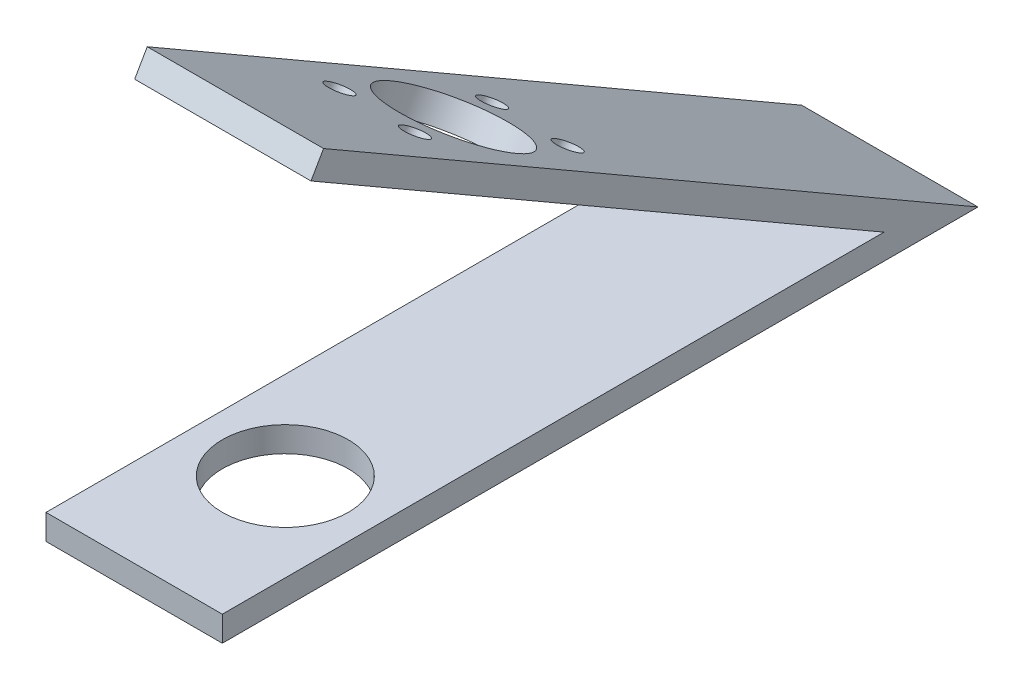
SolidWorks part; units mm, degrees
ref_plane "Front Plane" through (0, 0, 0) normal (0, 0, 1) x (1, 0, 0)
ref_plane "Top Plane" through (0, 0, 0) normal (0, 1, 0) x (1, 0, 0)
ref_plane "Right Plane" through (0, 0, 0) normal (1, 0, 0) x (0, 0, -1)
sketch "Sketch1" plane through (0, 0, 0) normal (1, 0, 0) x (0, 0, -1)
  line L0 (-227.4871, 131.3397) -> (0, 0)
  line L1 (0, 0) -> (-262.6795, 0)
  line L2 (-262.6795, 0) -> (-262.6795, -10)
  line L3 (-262.6795, -10) -> (37.3205, -10)
  line L4 (37.3205, -10) -> (-222.4871, 140)
  line L5 (-222.4871, 140) -> (-227.4871, 131.3397)
  dimension "D1" = 10
  dimension "D2" = 10
  dimension "D3" = 300
  dimension "D4" = 300
  dimension "D5" = 30
extrude "Boss-Extrude1" add sketch "Sketch1" along normal blind 70
sketch "Sketch2" plane through (0, 8.6603, -5) normal (0, 0.866, -0.5) x (1, 0, 0)
  line L0 (0, 37.3205) -> (0, -262.6795) construction
  line L4 (70, -262.6795) -> (0, -262.6795) construction
  circle A0 centre (35, -162.6795) radius 25
  dimension "D1" = 50
  dimension "D2" = 35
  dimension "D3" = 100
extrude "Cut-Extrude1" cut sketch "Sketch2" against normal blind 10
sketch "Sketch5" plane through (0, 0, 0) normal (0, 1, 0) x (1, 0, 0)
  line L0 (70, -262.6795) -> (0, -262.6795) construction
  line L1 (70, 37.3205) -> (70, -222.4871) construction
  circle A0 centre (35, -202.6795) radius 25
  dimension "D1" = 50
  dimension "D2" = 60
  dimension "D3" = 35
extrude "Cut-Extrude3" cut sketch "Sketch5" against normal blind 300
sketch "Sketch6" plane through (0, 8.6603, -5) normal (0, 0.866, -0.5) x (1, 0, 0)
  line L5 (70, 37.3205) -> (70, -262.6795) construction
  line L6 (0, 37.3205) -> (0, -262.6795) construction
  circle A0 centre (50, -197.6795) radius 5
  circle A1 centre (20, -197.6795) radius 5
  circle A2 centre (20, -127.6795) radius 5
  circle A3 centre (50, -127.6795) radius 5
  point P0 (35, -162.6795)
  dimension "D2" = 10
  dimension "D3" = 10
  dimension "D4" = 10
  dimension "D5" = 10
  dimension "D1" = 20
  dimension "D6" = 20
  dimension "D7" = 20
  dimension "D8" = 20
extrude "Cut-Extrude5" cut sketch "Sketch6" against normal blind 10
equation "\"mountAngle\" = 30deg"
equation "\"D5@Sketch1\"=\"mountAngle\""
equation "\"ThrusterDim\"= 140mm"
equation "\"hatchHoleDiameter\"= 600mm"
equation "\"hullThickness\"= 120mm"
equation "\"gasketHullInterconnectWidth\"= 100mm"
equation "\"collarThickness\"= 15"
equation "\"hatchTunnelLength\"=200"
equation "\"oRingDiameter\"=2"
equation "\"boltPatternRadiusInterconnect\"=500"
equation "\"interconnectBoltDiameter\"=30"
equation "\"hatchShaftDiameter\"=20"
equation "\"hatchMinima\"=50"
equation "\"hullDiameter\"=2000"
equation "\"hatchMaxima\"=180"
equation "\"bushingFlatHatch\"=15"
equation "\"hingePivotDiameter\"=20"
equation "\"handleWidth\"=250"
equation "\"handleHeight\"=160"
equation "\"handleThickness\"=25"
equation "\"FrameLength\"= 4300"
equation "\"FrameMidLength\"= 3000"
equation "\"TubeOD\"= 100"
equation "\"FrameBackFlat\"= 800"
equation "\"TubeWall\"=15"
equation "\"TopMemberAngle\"=120"
equation "\"FrameHight\"= 2500"
